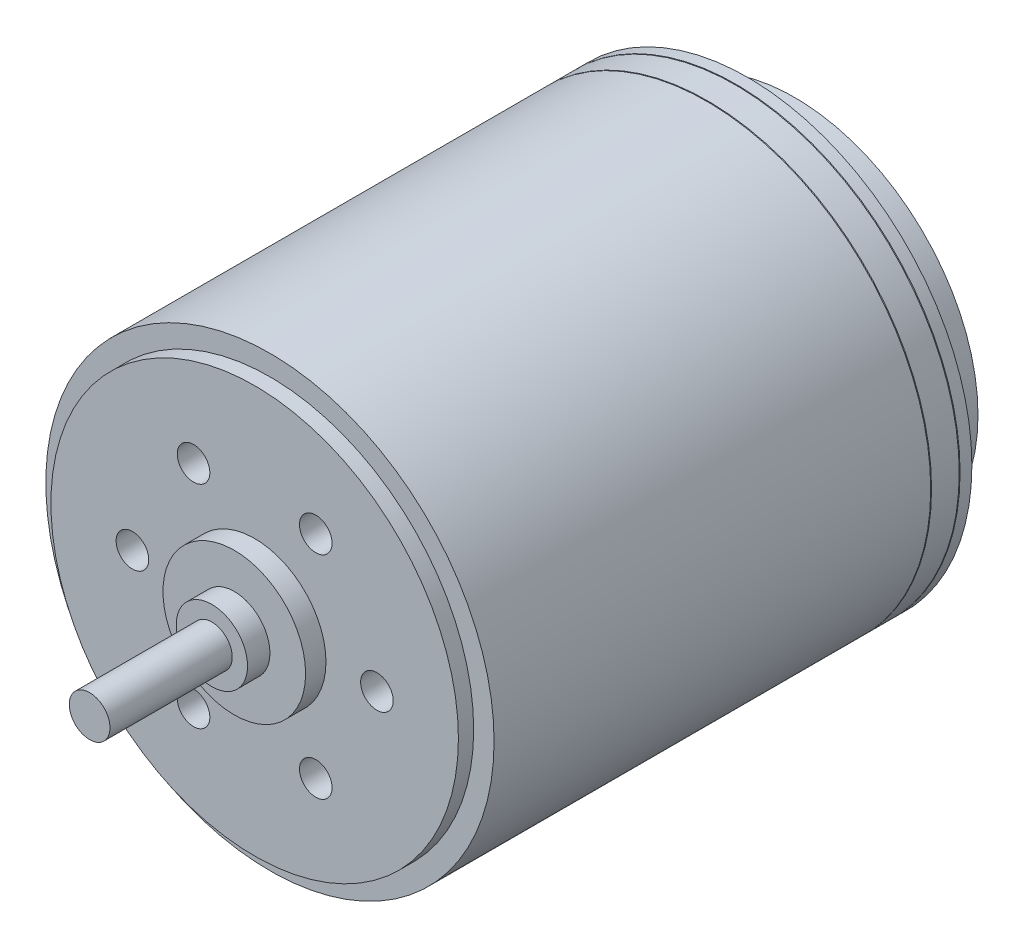
SolidWorks part; units mm, degrees
ref_plane "Front Plane" through (0, 0, 0) normal (0, 0, 1) x (1, 0, 0)
ref_plane "Top Plane" through (0, 0, 0) normal (0, 1, 0) x (1, 0, 0)
ref_plane "Right Plane" through (0, 0, 0) normal (1, 0, 0) x (0, 0, -1)
sketch "Sketch1" plane through (0, 0, 0) normal (0, 1, 0) x (1, 0, 0)
  line L0 (11, 0) -> (0, 0)
  line L1 (0, 0) -> (0, -23.45)
  line L2 (0, -23.45) -> (11, -23.45)
  line L3 (11, -23.45) -> (11, -2.0207)
  line L4 (11, -2.0207) -> (10.95, -2)
  line L5 (10.95, -2) -> (11, -1.9793)
  line L6 (11, -1.9793) -> (11, -0.6207)
  line L7 (11, -0.6207) -> (10.95, -0.6)
  line L8 (10.95, -0.6) -> (11, -0.5793)
  line L9 (11, -0.5793) -> (11, 0)
  line L10 (0, 0) -> (0, -23.45) construction
revolve "Revolve1" add sketch "Sketch1" angle 360 about L10 reverse direction yes
sketch "Sketch6" plane through (0, 0, 0) normal (0, 0, -1) x (-1, 0, 0)
  line L0 (5.05, 5.4772) -> (5.05, -5.4772)
  line L1 (-5.05, -5.4772) -> (-5.05, 5.4772)
  arc A0 (-5.05, 5.4772) -> (5.05, 5.4772) centre (0, 0) cw
  arc A1 (5.05, -5.4772) -> (-5.05, -5.4772) centre (0, 0) cw
extrude "Boss-Extrude3" add sketch "Sketch6" along normal blind 1
sketch "Sketch7" plane through (0, 0, 23.45) normal (0, 0, 1) x (1, 0, 0)
  circle A0 centre (0, 0) radius 10
extrude "Boss-Extrude4" add sketch "Sketch7" along normal blind 0.75
sketch "Sketch8" plane through (0, 0, 24.2) normal (0, 0, 1) x (1, 0, 0)
  circle A0 centre (0, 0) radius 3.5
extrude "Boss-Extrude5" add sketch "Sketch8" along normal blind 1
sketch "Sketch9" plane through (0, 0, 25.2) normal (0, 0, 1) x (1, 0, 0)
  circle A0 centre (0, 0) radius 1.75
extrude "Boss-Extrude6" add sketch "Sketch9" along normal blind 1.1
sketch "Sketch10" plane through (0, 0, 26.3) normal (0, 0, 1) x (1, 0, 0)
  circle A0 centre (0, 0) radius 1
extrude "Boss-Extrude7" add sketch "Sketch10" along normal blind 6
hole_wizard "Ø1.6 (1.6) Diameter Hole1" positions "Sketch12" profile "Sketch11" hole size "Ø1.6" standard "ANSI Metric"
sketch "Sketch12" plane through (0, 0, 24.2) normal (0, 0, 1) x (1, 0, 0)
  point P0 (-3, 5.1962)
  point P1 (3, 5.1962)
  point P2 (6, 0)
  point P3 (3, -5.1962)
  point P4 (-3, -5.1962)
  point P5 (-6, 0)
sketch "Sketch11" plane through (-3, 5.1962, 24.2) normal (1, 0, 0) x (0, -1, 0)
  line L0 (0, 0) -> (0, 4.9807)
  line L1 (0, 4.9807) -> (0.8, 4.5)
  line L2 (0.8, 4.5) -> (0.8, 0)
  line L5 (0.8, 0) -> (0, 0)
  line L10 (0, 4.9807) -> (-0.8, 4.5) construction
  line L11 (0, -6.35) -> (0, 107.95) construction
  dimension "Hole Dia." = 1.6
  dimension "Hole Depth" = 4.5
  dimension "Drill Angle" = 118
sketch "Sketch13" plane through (0, 0, 0) normal (0, 0, -1) x (-1, 0, 0)
  circle A0 centre (0, 0) radius 9
extrude "Boss-Extrude8" add sketch "Sketch13" along normal blind 2.3
